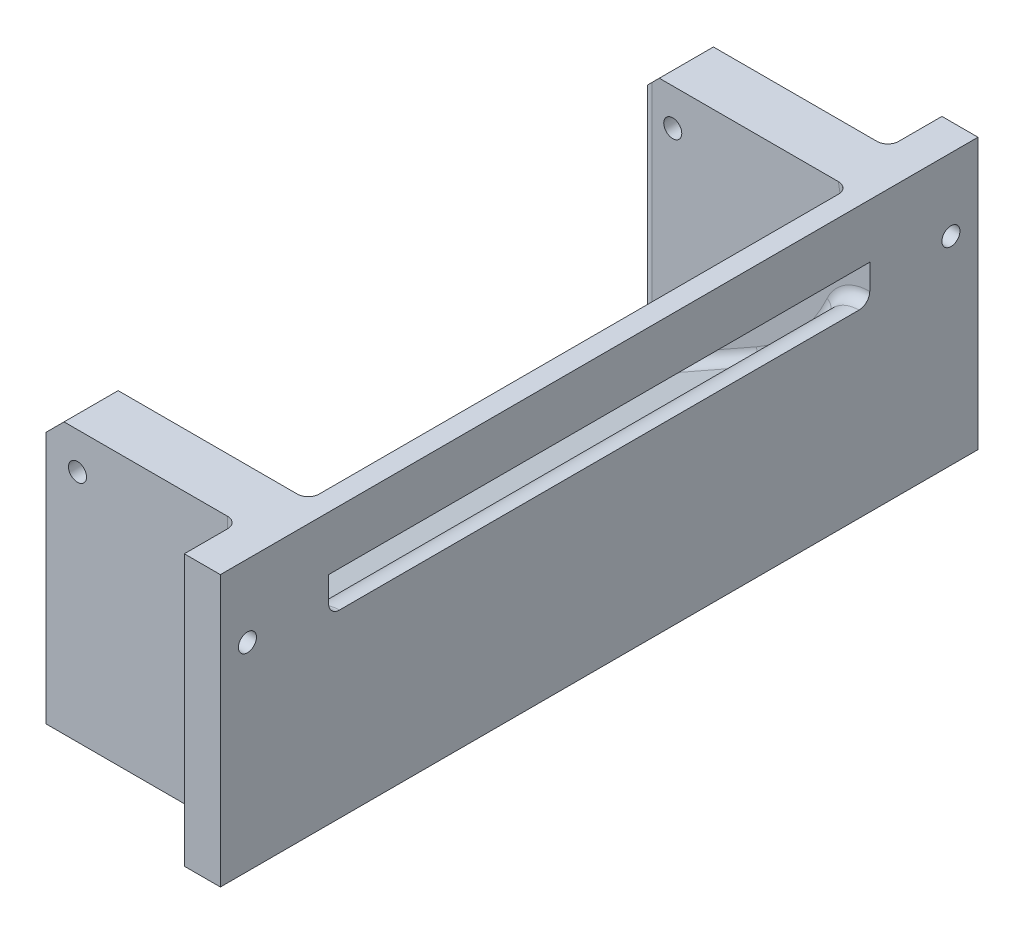
SolidWorks part; units mm, degrees
ref_plane "Front Plane" through (0, 0, 0) normal (0, 0, 1) x (1, 0, 0)
ref_plane "Top Plane" through (0, 0, 0) normal (0, 1, 0) x (1, 0, 0)
ref_plane "Right Plane" through (0, 0, 0) normal (1, 0, 0) x (0, 0, -1)
sketch "Sketch2" plane through (0, 0, 0) normal (0, 0, 1) x (1, 0, 0)
  line L1 (8.9403, -47.3788) -> (8.9403, -44.8788)
  line L2 (8.9403, -44.8788) -> (42.2565, -26.0606)
  line L4 (72.2767, 2.6212) -> (72.2767, -47.3788)
  line L5 (8.9403, -47.3788) -> (72.2767, -47.3788)
  arc A0 (72.2767, 2.6212) -> (63.175, -3.2366) centre (72.2767, -7.3788) ccw
  arc A1 (42.2565, -26.0606) -> (63.175, -3.2366) centre (17.6663, 17.4746) ccw
  dimension "D2" = 50
  dimension "D4" = 10
  dimension "D1" = 2.5
  dimension "D3" = 50
extrude "Boss-Extrude2" add sketch "Sketch2" along normal mid plane 150 separate body
sketch "Sketch4" plane through (0, 0, -75) normal (0, 0, -1) x (-1, 0, 0)
  line L2 (-72.2767, -47.3788) -> (-8.9403, -47.3788)
  line L3 (-72.2767, -47.3788) -> (-72.2767, 27.6212)
  line L4 (-72.2767, 27.6212) -> (-8.9403, 27.6212)
  line L5 (-8.9403, -47.3788) -> (-8.9403, 27.6212)
  line L6 (-8.9403, -44.8788) -> (-8.9403, -47.3788) construction
  line L8 (-8.9403, -47.3788) -> (-72.2767, -47.3788) construction
  line L9 (-72.2767, -47.3788) -> (-72.2767, 2.6212) construction
  dimension "D1" = 75
extrude "Boss-Extrude3" add sketch "Sketch4" along normal blind 15
mirror "Mirror1" about plane through (0, 0, 0) normal (0, 0, 1) of "Boss-Extrude3"
sketch "Sketch6" plane through (72.2767, 0, 0) normal (1, 0, 0) x (0, 0, -1)
  line L1 (-90, 27.6212) -> (-105, 27.6212)
  line L2 (-90, 27.6212) -> (-90, -47.3788)
  line L3 (-90, -47.3788) -> (-105, -47.3788)
  line L4 (-105, 27.6212) -> (-105, -47.3788)
  line L5 (0, 0) -> (0, -65.9992) construction
  line L6 (105, 27.6212) -> (105, -47.3788)
  line L7 (90, -47.3788) -> (105, -47.3788)
  line L8 (90, 27.6212) -> (90, -47.3788)
  line L9 (90, 27.6212) -> (105, 27.6212)
  line L10 (-90, -47.3788) -> (90, -47.3788) construction
  circle A0 centre (-97.5, 7.6212) radius 2.5
  circle A3 centre (97.5, 7.6212) radius 2.5
  dimension "D2" = 5
  dimension "D1" = 15
  dimension "D4" = 20
  dimension "D6" = 7.5
extrude "Boss-Extrude4" add sketch "Sketch6" against normal blind 10
sketch "Sketch7" plane through (0, 0, -75) normal (0, 0, 1) x (1, 0, 0)
  arc A0 (42.2565, -26.0606) -> (63.175, -3.2366) centre (17.6663, 17.4746) ccw construction
  arc A1 (42.2565, -26.0606) -> (63.175, -3.2366) centre (17.6663, 17.4746) ccw construction
  circle A2 centre (17.6663, 17.4746) radius 2.5
  dimension "D1" = 5
extrude "Cut-Extrude1" cut sketch "Sketch7" against normal through all both and the other way through all
sketch "Sketch9" plane through (0, 0, -75) normal (0, 0, 1) x (1, 0, 0)
  line L0 (66.6259, 27.6212) -> (72.2767, 27.6212)
  line L1 (72.2767, 12.6212) -> (67.4301, 12.6212)
  line L3 (72.2767, 27.6212) -> (72.2767, 2.6212) construction
  line L5 (72.2767, 27.6212) -> (72.2767, 12.6212)
  arc A0 (66.6259, 27.6212) -> (67.4301, 12.6212) centre (17.6663, 17.4746) cw construction
  arc A1 (66.6259, 27.6212) -> (67.4301, 12.6212) centre (17.6663, 17.4746) cw
  dimension "D1" = 50
  dimension "D3" = 5.6508
  dimension "D2" = 10
extrude "Boss-Extrude5" add sketch "Sketch9" along normal up to next
chamfer "Chamfer1" distance 5 angle 45 2 edges at (8.9403, 27.6212, 82.5) (8.9403, 27.6212, -82.5)
fillet "Fillet1" radius 3 13 edges at (8.9403, -44.8788, 0) (62.2767, -9.8788, 90) (62.2767, -9.8788, -90) (8.9403, -11.1288, -75) (8.9403, -11.1288, 75) (25.5984, -35.4697, -75) (54.5268, -16.3085, -75) (25.5984, -35.4697, 75) (54.5268, -16.3085, 75) (66.8648, 1.0302, -75) (66.8648, 1.0302, 75) (67.5945, 20.1515, 75) (67.5945, 20.1515, -75)
